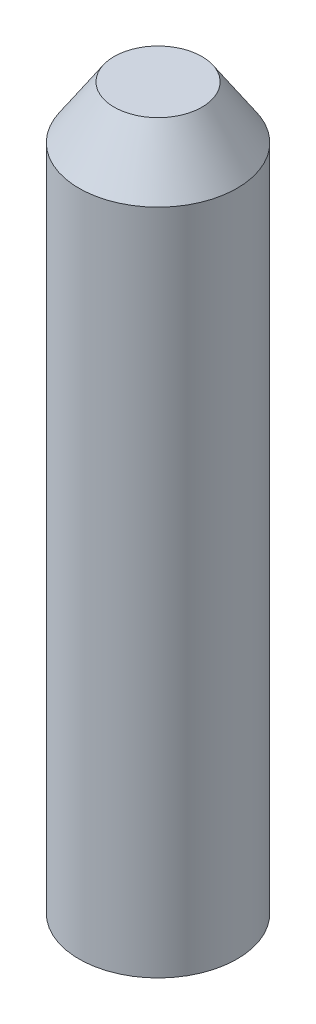
SolidWorks part; units mm, degrees
ref_plane "Спереди" through (0, 0, 0) normal (0, 0, 1) x (1, 0, 0)
ref_plane "Сверху" through (0, 0, 0) normal (0, 1, 0) x (1, 0, 0)
ref_plane "Справа" through (0, 0, 0) normal (1, 0, 0) x (0, 0, -1)
sketch "Эскиз2" plane through (0, 0, 0) normal (0, 0, 1) x (1, 0, 0)
  line L0 (0, 0) -> (0, 41)
  line L1 (0, 41) -> (2.5, 41)
  line L2 (2.5, 41) -> (4.5, 38)
  line L3 (4.5, 38) -> (4.5, 0)
  line L4 (4.5, 0) -> (0, 0)
  dimension "D1" = 4.5
  dimension "D2" = 41
  dimension "D3" = 3
  dimension "D4" = 2.5
revolve "База" add sketch "Эскиз2" angle 360 about L0
sketch "Эскиз3" plane through (0, 0, 0) normal (0, -1, 0) x (1, 0, 0)
  circle A0 centre (0, 0) radius 4
  circle A1 centre (0, 0) radius 2.25
  dimension "D1" = 8
  dimension "D2" = 4.5
extrude "Вырез-Вытянуть1" cut sketch "Эскиз3" against normal blind 1.5
